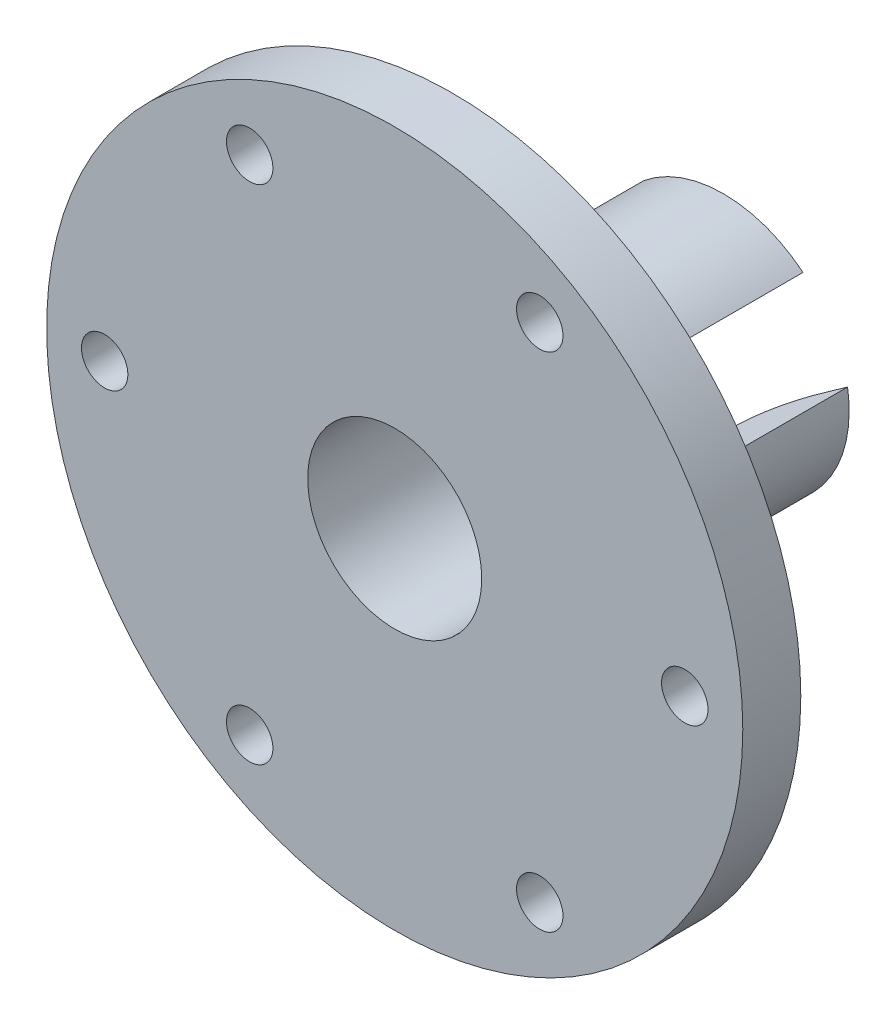
SolidWorks part; units mm, degrees
ref_plane "Front Plane" through (0, 0, 0) normal (0, 0, 1) x (1, 0, 0)
ref_plane "Top Plane" through (0, 0, 0) normal (0, 1, 0) x (1, 0, 0)
ref_plane "Right Plane" through (0, 0, 0) normal (1, 0, 0) x (0, 0, -1)
sketch "Sketch1" plane through (0, 0, 0) normal (0, 0, 1) x (1, 0, 0)
  circle A4 centre (0, 0) radius 10
  circle A5 centre (0, 0) radius 18
  dimension "D1" = 20
  dimension "D2" = 8
extrude "Boss-Extrude1" add sketch "Sketch1" along normal blind 3 contours A5 A4 | A4 region at (0, 0, 0) region at (-17.4909, 0, 0)
hole_wizard "M2 Clearance Hole2" positions "Sketch4" profile "Sketch5" hole size "M2" standard "ANSI Metric" end condition up to next
sketch "Sketch4" plane through (0, 0, 0) normal (0, 0, -1) x (-1, 0, 0)
  circle A3 centre (0, 0) radius 15
  point P42 (-15, 0)
  point P48 (-7.5, 12.9904)
  point P49 (7.5, 12.9904)
  point P50 (15, 0)
  point P51 (7.5, -12.9904)
  point P52 (-7.5, -12.9904)
  dimension "D1" = 30
sketch "Sketch5" plane through (7.5, -12.9904, 0) normal (1, 0, 0) x (0, 1, 0)
  line L0 (0, 0) -> (0, 3)
  line L1 (0, 3) -> (1.2, 3)
  line L2 (1.2, 3) -> (1.2, 0)
  line L5 (1.2, 0) -> (0, 0)
  line L11 (0, -6.35) -> (0, 107.95) construction
  dimension "Thru Hole Dia." = 2.4
  dimension "Thru Hole Depth" = 3
sketch "Sketch6" plane through (0, 0, 0) normal (0, 0, 1) x (1, 0, 0)
  circle A0 centre (0, 0) radius 6.5
  circle A1 centre (0, 0) radius 4.5
  circle A2 centre (0, 0) radius 9.5
  dimension "D1" = 13
  dimension "D2" = 2
  dimension "D3" = 3
extrude "Boss-Extrude2" add sketch "Sketch6" against normal blind 15 contours A0 A1 region at (-6.3162, 0, 0)
extrude "Cut-Extrude2" cut sketch "Sketch6<2>" along normal through all contours A1 region at (0, 0, 0)
sketch "Sketch6<2>" plane through (0, 0, 0) normal (0, 0, 1) x (1, 0, 0) same geometry as "Sketch6"
extrude "Boss-Extrude3" add sketch "Sketch6<4>" against normal blind 2.5 contours A2 A0 region at (-9.2313, 0, 0)
sketch "Sketch6<4>" plane through (0, 0, 0) normal (0, 0, 1) x (1, 0, 0) same geometry as "Sketch6"
chamfer "Chamfer1" distance 1 angle 45 1 edges at (9.5, 0, -2.5)
sketch "Sketch7" plane through (0, 0, 3) normal (0, 0, 1) x (1, 0, 0)
  circle A0 centre (0, 0) radius 21
  circle A1 centre (0, 0) radius 22.5
  dimension "D1" = 42
  dimension "D2" = 1.5
extrude "Boss-Extrude4" [suppressed] add sketch "Sketch7" along normal blind 1
chamfer "Chamfer2" distance 3 angle 45 1 edges at (4.5, 0, -15)
sketch "Sketch8" plane through (0, 0, -2.5) normal (0, 0, -1) x (-1, 0, 0)
  line L0 (0, -10.8928) -> (0, 0) construction
  line L1 (0, 0) -> (-11.1503, 6.4377) construction
  line L2 (0, 0) -> (11.0083, 6.3556) construction
  line L3 (-6.415, 1.0479) -> (-4.4911, 0.2835)
  line L4 (-4.115, 5.0316) -> (-2.4911, 3.7476)
  arc A0 (-6.415, 1.0479) -> (-4.115, 5.0316) centre (0, 0) cw
  circle A2 centre (0, 0) radius 6.5 construction
  arc A3 (-4.4911, 0.2835) -> (-2.4911, 3.7476) centre (0, 0) cw
  circle A4 centre (0, 0) radius 4.5 construction
  dimension "D3" = 4.6
  dimension "D1" = 120
  dimension "D2" = 120
  dimension "D4" = 4
extrude "Cut-Extrude3" cut sketch "Sketch8" along normal blind 16 from offset 5
pattern_circular "CirPattern1" count 3 over 360 about axis through (0, 0, -12) along (0, 0, -1) of "Cut-Extrude3"
chamfer "Chamfer3" distance 3 angle 30 3 edges at (3.8971, 2.25, -7.5) (0, -4.5, -7.5) (-3.8971, 2.25, -7.5) first distance on face at (4.5, 0, 3)
fillet "Fillet2" radius 5 3 edges at (-3.8971, -2.25, -12) (3.8971, -2.25, -12) (0, 4.5, -12)
fillet "Fillet3" radius 1 6 edges
fillet "Fillet4" radius 1 9 edges at (-1.9037, -5.7137, -7.5) (1.8672, -5.7608, -7.5) (-3.9964, 4.5055, -7.5) (-5.9225, 1.2634, -7.5) (5.9, 1.2082, -7.5) (4.0554, 4.4974, -7.5) (0, -6.2321, -7.5) (-5.3971, 3.116, -7.5) (5.3971, 3.116, -7.5)
